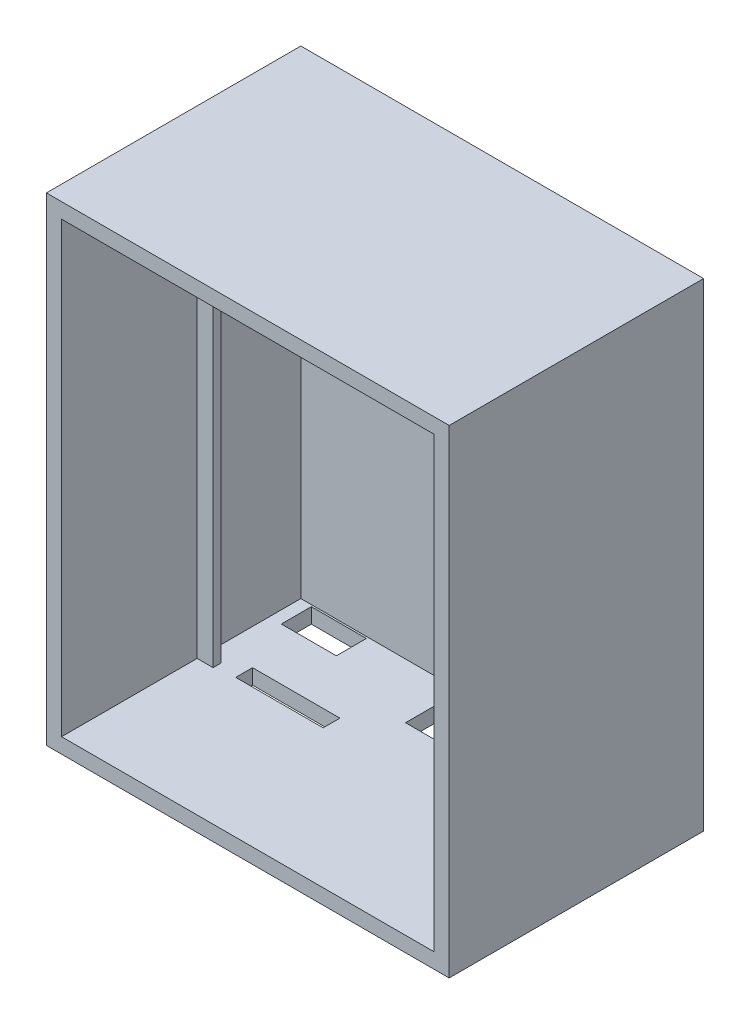
SolidWorks part; units mm, degrees
ref_plane "Piano frontale" through (0, 0, 0) normal (0, 0, 1) x (1, 0, 0)
ref_plane "Piano superiore" through (0, 0, 0) normal (0, 1, 0) x (1, 0, 0)
ref_plane "Piano destro" through (0, 0, 0) normal (1, 0, 0) x (0, 0, -1)
sketch "Schizzo1" plane through (0, 0, 0) normal (0, 0, 1) x (1, 0, 0)
  line L1 (0, 0) -> (50.5, 0)
  line L2 (0, 0) -> (0, 60)
  line L3 (0, 60) -> (50.5, 60)
  line L4 (50.5, 0) -> (50.5, 60)
  dimension "D1" = 50.5
  dimension "D2" = 60
extrude "Estrusione-Estrusione1" add sketch "Schizzo1" along normal blind 1.9
sketch "Schizzo2" plane through (0, 0, 1.9) normal (0, 0, 1) x (1, 0, 0)
  line L0 (0, 0) -> (50.5, 0) construction
  line L1 (0, 60) -> (1.9, 60)
  line L2 (0, 60) -> (0, 0)
  line L3 (0, 0) -> (1.9, 0)
  line L4 (1.9, 60) -> (1.9, 0)
  dimension "D1" = 1.9
extrude "Estrusione-Estrusione2" add sketch "Schizzo2" along normal blind 30
sketch "Schizzo3" plane through (0, 0, 1.9) normal (0, 0, 1) x (1, 0, 0)
  line L0 (50.5, 0) -> (50.5, 60) construction
  line L1 (1.9, 0) -> (50.5, 0)
  line L2 (1.9, 0) -> (1.9, 1.9)
  line L3 (1.9, 1.9) -> (50.5, 1.9)
  line L4 (50.5, 0) -> (50.5, 1.9)
  dimension "D1" = 1.9
extrude "Estrusione-Estrusione3" add sketch "Schizzo3" along normal blind 30
sketch "Schizzo4" plane through (0, 0, 1.9) normal (0, 0, 1) x (1, 0, 0)
  line L0 (50.5, 60) -> (1.9, 60) construction
  line L1 (50.5, 1.9) -> (48.6, 1.9)
  line L2 (50.5, 1.9) -> (50.5, 60)
  line L3 (50.5, 60) -> (48.6, 60)
  line L4 (48.6, 1.9) -> (48.6, 60)
  dimension "D1" = 1.9
extrude "Estrusione-Estrusione4" add sketch "Schizzo4" along normal blind 30
sketch "Schizzo5" plane through (0, 0, 1.9) normal (0, 0, 1) x (1, 0, 0)
  line L0 (48.6, 60) -> (48.6, 1.9) construction
  line L1 (1.9, 60) -> (48.6, 60)
  line L2 (1.9, 60) -> (1.9, 58.1)
  line L3 (1.9, 58.1) -> (48.6, 58.1)
  line L4 (48.6, 60) -> (48.6, 58.1)
  dimension "D1" = 1.9
extrude "Estrusione-Estrusione5" add sketch "Schizzo5" along normal blind 30
sketch "Schizzo6" plane through (0, 0, 1.9) normal (0, 0, 1) x (1, 0, 0)
  line L0 (48.6, 40.9769) -> (44, 40.9769)
  line L1 (48.6, 58.1) -> (48.6, 1.9) construction
  line L2 (44, 40.9769) -> (44, 1.9)
  line L3 (48.6, 1.9) -> (1.9, 1.9) construction
  line L4 (44, 1.9) -> (48.6, 1.9)
  line L5 (48.6, 1.9) -> (48.6, 40.9769)
  dimension "D1" = 4.6
extrude "Estrusione-Estrusione6" add sketch "Schizzo6" along normal blind 13
sketch "Schizzo7" plane through (0, 0, 1.9) normal (0, 0, 1) x (1, 0, 0)
  line L0 (1.9, 1.9) -> (1.9, 58.1) construction
  line L1 (1.9, 43.9691) -> (25.3766, 43.9691)
  line L2 (1.9, 43.9691) -> (1.9, 48.629)
  line L3 (1.9, 48.629) -> (25.3766, 48.629)
  line L4 (25.3766, 43.9691) -> (25.3766, 48.629)
extrude "Estrusione-Estrusione7" add sketch "Schizzo7" along normal blind 13
sketch "Schizzo8" plane through (1.9, 0, 0) normal (1, 0, 0) x (0, 0, -1)
  line L0 (-31.9, 1.9) -> (-1.9, 1.9) construction
  line L1 (-14.9, 43.9691) -> (-13.9, 43.9691)
  line L2 (-14.9, 43.9691) -> (-14.9, 1.9)
  line L3 (-14.9, 1.9) -> (-13.9, 1.9)
  line L4 (-13.9, 43.9691) -> (-13.9, 1.9)
  dimension "D1" = 1
extrude "Estrusione-Estrusione8" add sketch "Schizzo8" along normal blind 2
sketch "Schizzo9" plane through (48.6, 0, 0) normal (-1, 0, 0) x (0, 0, 1)
  line L0 (31.9, 58.1) -> (1.9, 58.1) construction
  line L1 (14.9, 40.9769) -> (13.4, 40.9769)
  line L2 (14.9, 40.9769) -> (14.9, 58.1)
  line L3 (14.9, 58.1) -> (13.4, 58.1)
  line L4 (13.4, 40.9769) -> (13.4, 58.1)
  dimension "D1" = 1.5
extrude "Estrusione-Estrusione9" add sketch "Schizzo9" along normal blind 4
sketch "Schizzo10" plane through (1.9, 0, 0) normal (1, 0, 0) x (0, 0, -1)
  line L0 (-31.9, 58.1) -> (-1.9, 58.1) construction
  line L1 (-14.9, 48.629) -> (-13.4, 48.629)
  line L2 (-14.9, 48.629) -> (-14.9, 58.1)
  line L3 (-14.9, 58.1) -> (-13.4, 58.1)
  line L4 (-13.4, 48.629) -> (-13.4, 58.1)
  dimension "D1" = 1.5
extrude "Estrusione-Estrusione10" add sketch "Schizzo10" along normal blind 4
sketch "Schizzo11" plane through (0, 0, 0) normal (0, -1, 0) x (-1, 0, 0)
  line L1 (-3.4392, -5.8852) -> (-10.3444, -5.8852)
  line L2 (-3.4392, -5.8852) -> (-3.4392, -2.1208)
  line L3 (-3.4392, -2.1208) -> (-10.3444, -2.1208)
  line L4 (-10.3444, -5.8852) -> (-10.3444, -2.1208)
extrude "Taglio-Estrusione1" cut sketch "Schizzo11" against normal blind 2
sketch "Schizzo13" plane through (0, 0, 0) normal (0, -1, 0) x (-1, 0, 0)
  line L1 (-37.8471, -8.8172) -> (-21.9434, -8.8172)
  line L2 (-37.8471, -8.8172) -> (-37.8471, -3.9519)
  line L3 (-37.8471, -3.9519) -> (-21.9434, -3.9519)
  line L4 (-21.9434, -8.8172) -> (-21.9434, -3.9519)
extrude "Taglio-Estrusione2" cut sketch "Schizzo13" against normal blind 2
sketch "Schizzo14" plane through (0, 0, 0) normal (0, -1, 0) x (1, 0, 0)
  line L1 (6.3759, 14.5379) -> (17.3347, 14.5379)
  line L2 (6.3759, 14.5379) -> (6.3759, 12.4313)
  line L3 (6.3759, 12.4313) -> (17.3347, 12.4313)
  line L4 (17.3347, 14.5379) -> (17.3347, 12.4313)
extrude "Taglio-Estrusione3" cut sketch "Schizzo14" against normal blind 2
